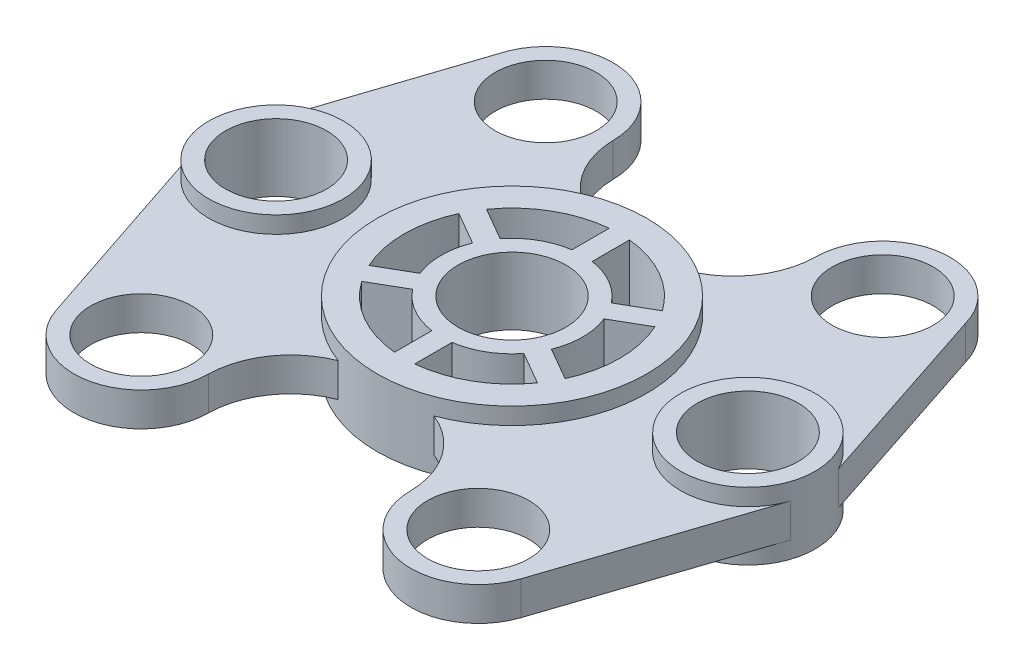
SolidWorks part; units mm, degrees
ref_plane "Front Plane" through (0, 0, 0) normal (0, 0, 1) x (1, 0, 0)
ref_plane "Top Plane" through (0, 0, 0) normal (0, 1, 0) x (1, 0, 0)
ref_plane "Right Plane" through (0, 0, 0) normal (1, 0, 0) x (0, 0, -1)
sketch "Sketch1" plane through (0, 0, 0) normal (0, 1, 0) x (1, 0, 0)
  line L0 (0, 102.7484) -> (0, -41393.4706) construction
  line L1 (1.2798, 0) -> (-41395.4818, 0) construction
  line L2 (-3, -20.7846) -> (-3, -31.8591)
  line L3 (3, -20.7846) -> (3, -31.8591)
  line L4 (-16.5, -12.9904) -> (-26.0908, -18.5276)
  line L5 (-19.5, -7.7942) -> (-29.0908, -13.3315)
  line L6 (-19.5, 7.7942) -> (-29.0908, 13.3315)
  line L7 (-16.5, 12.9904) -> (-26.0908, 18.5276)
  line L8 (-3, 20.7846) -> (-3, 31.8591)
  line L9 (3, 20.7846) -> (3, 31.8591)
  line L10 (16.5, 12.9904) -> (26.0908, 18.5276)
  line L11 (19.5, 7.7942) -> (29.0908, 13.3315)
  line L12 (19.5, -7.7942) -> (29.0908, -13.3315)
  line L13 (16.5, -12.9904) -> (26.0908, -18.5276)
  line L14 (69.2801, 65.3178) -> (89.7055, 3.4195)
  line L15 (88.9737, -6.3246) -> (68.9737, -66.3246)
  line L16 (-88.9737, -6.3246) -> (-68.9737, -66.3246)
  line L17 (-69.2801, 65.3178) -> (-89.7055, 3.4195)
  circle A0 centre (0, 0) radius 16
  arc A1 (16.5, 12.9904) -> (3, 20.7846) centre (0, 0) ccw
  arc A2 (26.0908, 18.5276) -> (3, 31.8591) centre (0, 0) ccw
  circle A3 centre (0, 0) radius 40
  arc A4 (19.5, -7.7942) -> (19.5, 7.7942) centre (0, 0) ccw
  arc A5 (29.0908, -13.3315) -> (29.0908, 13.3315) centre (0, 0) ccw
  arc A6 (3, -20.7846) -> (16.5, -12.9904) centre (0, 0) ccw
  arc A7 (3, -31.8591) -> (26.0908, -18.5276) centre (0, 0) ccw
  arc A8 (-16.5, -12.9904) -> (-3, -20.7846) centre (0, 0) ccw
  arc A9 (-26.0908, -18.5276) -> (-3, -31.8591) centre (0, 0) ccw
  arc A10 (-29.0908, 13.3315) -> (-29.0908, -13.3315) centre (0, 0) ccw
  arc A11 (-19.5, 7.7942) -> (-19.5, -7.7942) centre (0, 0) ccw
  arc A12 (-3, 31.8591) -> (-26.0908, 18.5276) centre (0, 0) ccw
  arc A13 (-3, 20.7846) -> (-16.5, 12.9904) centre (0, 0) ccw
  circle A14 centre (50, 60) radius 15
  arc A15 (69.2801, 65.3178) -> (30, 60) centre (50, 60) ccw
  circle A16 centre (50, -60) radius 15
  arc A17 (68.9737, -66.3246) -> (30, -60) centre (50, -60) cw
  circle A18 centre (70, 0) radius 20
  circle A19 centre (70, 0) radius 15
  arc A20 (30, 60) -> (14.2215, 37.3865) centre (5.1426, 60.5327) cw
  arc A21 (30, -60) -> (14.2215, -37.3865) centre (5.1426, -60.5327) ccw
  arc A22 (-30, -60) -> (-14.2215, -37.3865) centre (-5.1426, -60.5327) cw
  circle A23 centre (-50, -60) radius 15
  arc A24 (-68.9737, -66.3246) -> (-30, -60) centre (-50, -60) ccw
  circle A25 centre (-70, 0) radius 15
  circle A26 centre (-70, 0) radius 20
  circle A27 centre (-50, 60) radius 15
  arc A28 (-69.2801, 65.3178) -> (-30, 60) centre (-50, 60) cw
  arc A29 (-30, 60) -> (-14.2215, 37.3865) centre (-5.1426, 60.5327) ccw
  point P14 (3, -26.3218)
  point P15 (0, 0)
  point P37 (0, 0)
  point P41 (0, -102.7484)
  point P51 (8.8793, 39.002)
  point P54 (30, 60.3142)
  point P55 (30.3842, -55.7843)
  point P56 (0, 0)
  point P58 (0, 0)
  point P59 (0, 0)
  point P60 (0, 0)
  point P61 (0, 0)
  point P62 (0, 0)
  point P63 (0, 0)
  point P64 (0, 0)
  point P65 (0, 0)
  point P66 (0, 0)
  point P67 (29.0908, 59.7436)
  point P87 (-11.4949, -38.3127)
  point P88 (-14.2215, 37.3865)
  dimension "D1" = 32
  dimension "D2" = 42
  dimension "D3" = 64
  dimension "D4" = 80
  dimension "D9" = 40
  dimension "D10" = 30
  dimension "D11" = 40
  dimension "D12" = 30
  dimension "D14" = 24.8631
  dimension "D5" = 6
  dimension "D7" = 50
  dimension "D8" = 60
  dimension "D13" = 20
  dimension "D6" = 6
extrude "Boss-Extrude4" add sketch "Sketch1" along normal mid plane 20 contours A25 | A3 A9 L4 A8 L2 A7 L3 A6 L13 A5 L12 A4 L11 A0 A2 L10 A1 L9 L6 A11 L5 A10 L8 A13 L7 A12 | A19 | A26 | A18 region at (31.9993, 0, -22.0639) region at (70, 0, 0) region at (-70, 0, 0)
extrude "Boss-Extrude5" add sketch "Sketch1<7>" along normal mid plane 10 contours A29 A28 L17 A26 L16 A24 A22 A3 A23 A27 | A21 A17 L15 A18 L14 A15 A20 A3 A14 A16 region at (76.8983, 0, -36.5955) region at (-41.766, 0, 0)
sketch "Sketch1<7>" plane through (0, 0, 0) normal (0, 1, 0) x (1, 0, 0) same geometry as "Sketch1"
